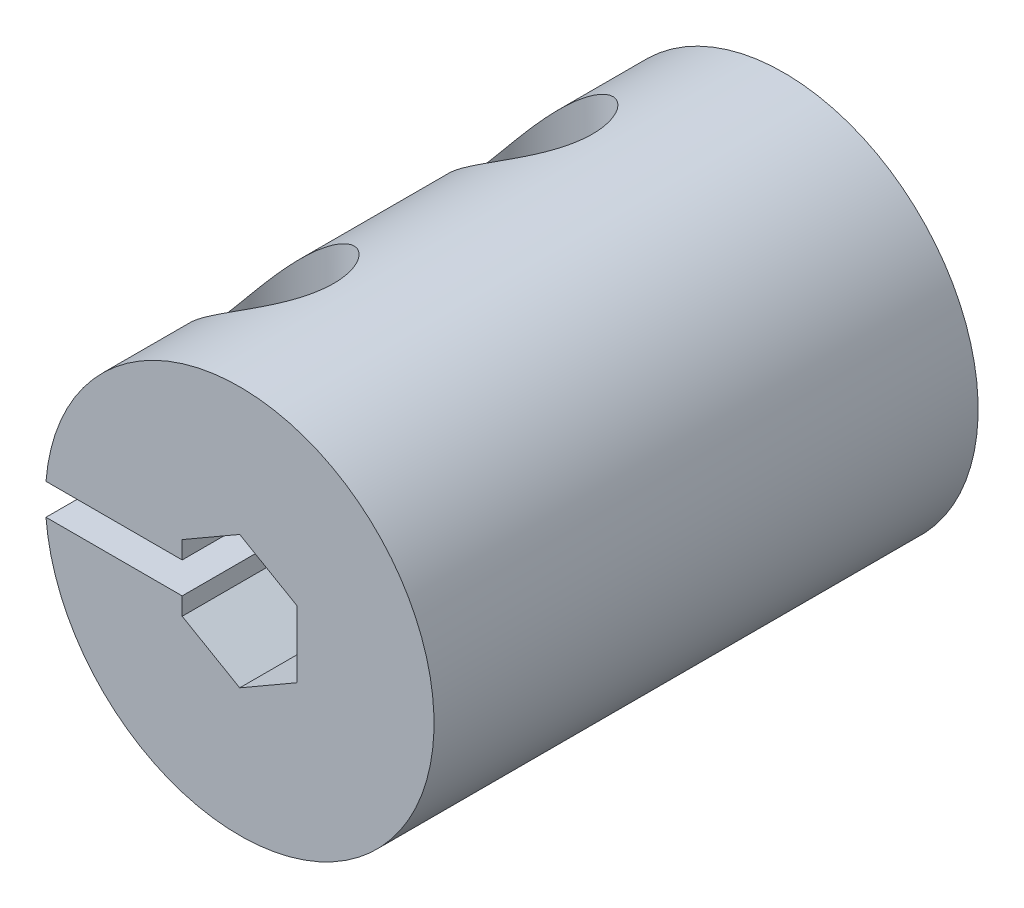
SolidWorks part; units mm, degrees
ref_plane "Front Plane" through (0, 0, 0) normal (0, 0, 1) x (1, 0, 0)
ref_plane "Top Plane" through (0, 0, 0) normal (0, 1, 0) x (1, 0, 0)
ref_plane "Right Plane" through (0, 0, 0) normal (1, 0, 0) x (0, 0, -1)
sketch "Sketch1" plane through (0, 0, 0) normal (0, 0, 1) x (1, 0, 0)
  line L0 (-20.2969, 1) -> (-3.7, 1)
  line L1 (-3.7, 2.1362) -> (-3.7, 1)
  line L2 (-3.7, -2.1362) -> (0, -4.2724)
  line L3 (0, -4.2724) -> (3.7, -2.1362)
  line L4 (3.7, -2.1362) -> (3.7, 2.1362)
  line L5 (3.7, 2.1362) -> (0, 4.2724)
  line L6 (0, 4.2724) -> (-3.7, 2.1362)
  line L7 (-3.7, 0) -> (-22.8855, 0) construction
  line L8 (-20.2969, -1) -> (-3.7, -1)
  line L9 (-20.2969, 1) -> (-20.2969, -1)
  line L10 (-3.7, -1) -> (-3.7, -2.1362)
  arc A0 (-1.85, -3.2043) -> (-1.85, 3.2043) centre (0, 0) ccw construction
  circle A1 centre (0, 0) radius 12.5
  dimension "D2" = 25
  dimension "D1" = 7.4
  dimension "D3" = 1
extrude "Boss-Extrude1" add sketch "Sketch1" along normal blind 35 contours L8 A1 L0 L1 L6 L5 L4 L3 L2 L10 region at (0.4863, 12.137, 0)
ref_plane "Plane1" through (0, 12.5, 0) normal (0, 1, 0) x (1, 0, 0)
sketch "Sketch2" plane through (0, 12.5, 0) normal (0, 1, 0) x (1, 0, 0)
  line L0 (-12.4599, 0) -> (-7.0788, -9.1755) construction
  line L1 (-7.0788, -9.1755) -> (-7.0788, -25.8245) construction
  line L2 (-7.0788, -25.8245) -> (-12.4599, -35) construction
  circle A0 centre (-7.0788, -9.1755) radius 1.8669
  circle A1 centre (-7.0788, -25.8245) radius 1.8669
  dimension "D1" = 3.7338
extrude "Cut-Extrude1" cut sketch "Sketch2" against normal through all
sketch "Sketch3" plane through (0, 12.5, 0) normal (0, 1, 0) x (1, 0, 0)
  circle A0 centre (-7.0788, -9.1755) radius 3.9497
  circle A1 centre (-7.0788, -25.8245) radius 3.9497
  dimension "D1" = 7.8994
extrude "Cut-Extrude2" cut sketch "Sketch3" against normal blind 8
ref_plane "Plane2" through (0, -12.5, 0) normal (0, -1, 0) x (-1, 0, 0)
sketch "Sketch4" plane through (0, -12.5, 0) normal (0, -1, 0) x (-1, 0, 0)
  line L1 (7.0788, -5.2307) -> (3.6625, -7.2031)
  line L2 (3.6625, -7.2031) -> (3.6625, -11.1479)
  line L3 (3.6625, -11.1479) -> (7.0788, -13.1203)
  line L4 (7.0788, -13.1203) -> (10.4951, -11.1479)
  line L5 (10.4951, -11.1479) -> (10.4951, -7.2031)
  line L6 (10.4951, -7.2031) -> (7.0788, -5.2307)
  line L7 (7.0788, -21.8797) -> (3.6625, -23.8521)
  line L8 (3.6625, -23.8521) -> (3.6625, -27.7969)
  line L9 (3.6625, -27.7969) -> (7.0788, -29.7693)
  line L10 (7.0788, -29.7693) -> (10.4951, -27.7969)
  line L11 (10.4951, -27.7969) -> (10.4951, -23.8521)
  line L12 (10.4951, -23.8521) -> (7.0788, -21.8797)
  circle A0 centre (7.0788, -9.1755) radius 3.4163 construction
  circle A1 centre (7.0788, -25.8245) radius 3.4163 construction
  dimension "D1" = 6.8326
extrude "Cut-Extrude3" cut sketch "Sketch4" against normal blind 8
